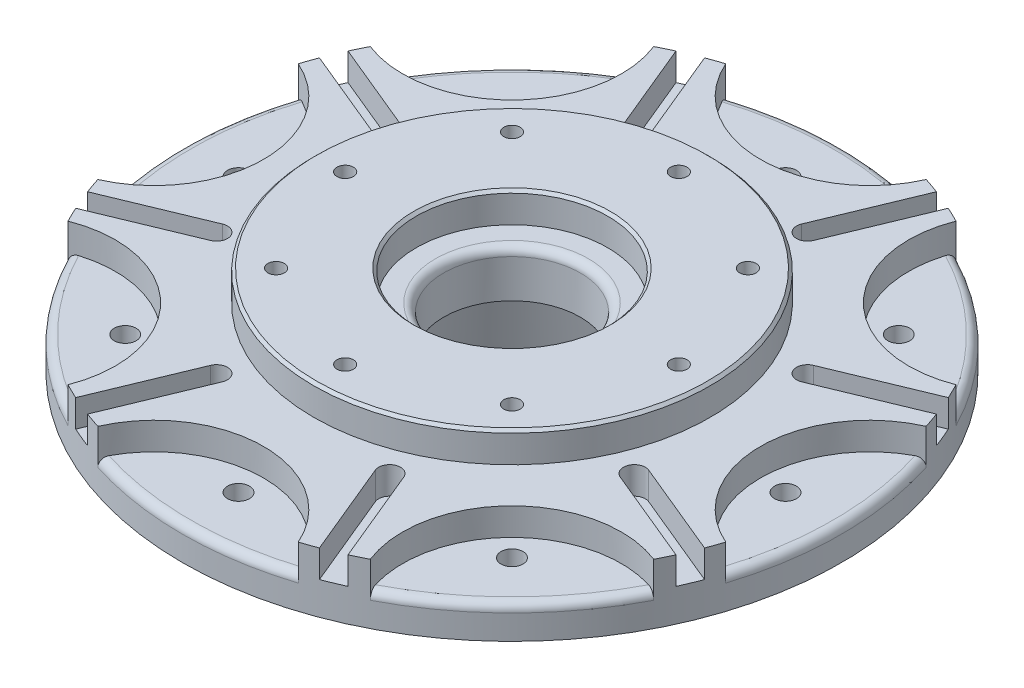
SolidWorks part; units mm, degrees
material "Plain Carbon Steel"
ref_plane "Front Plane" through (0, 0, 0) normal (0, 0, 1) x (1, 0, 0)
ref_plane "Top Plane" through (0, 0, 0) normal (0, 1, 0) x (1, 0, 0)
ref_plane "Right Plane" through (0, 0, 0) normal (1, 0, 0) x (0, 0, -1)
sketch "Sketch2" plane through (0, 0, 0) normal (0, 1, 0) x (1, 0, 0)
  circle A0 centre (0, 0) radius 72.5
  circle A1 centre (0, 0) radius 120.5
  dimension "D1" = 145
  dimension "D2" = 241
extrude "Boss-Extrude5" add sketch "Sketch2" along normal blind 11 contours A0 region at (0, 0, 0)
extrude "Boss-Extrude6" add sketch "Sketch2<8>" against normal blind 22 separate body contours A1 A0 region at (-117.0917, 0, 0)
sketch "Sketch2<8>" plane through (0, 0, 0) normal (0, 1, 0) x (1, 0, 0) same geometry as "Sketch2"
sketch "Sketch4" plane through (0, 0, 0) normal (0, -1, 0) x (1, 0, 0)
  circle A0 centre (0, 0) radius 74
extrude "Boss-Extrude7" add sketch "Sketch4" along normal blind 54
sketch "Sketch5" plane through (0, 11, 0) normal (0, 1, 0) x (1, 0, 0)
  circle A0 centre (0, 0) radius 35
  dimension "D1" = 70
extrude "Cut-Extrude2" cut sketch "Sketch5" against normal blind 11
sketch "Sketch6" plane through (0, 0, 0) normal (0, 1, 0) x (1, 0, 0)
  circle A0 centre (0, 0) radius 25
  dimension "D1" = 50
chamfer "Chamfer1" distance 1 angle 45 1 edges at (0, 11, 35)
extrude "Cut-Extrude3" cut sketch "Sketch6" against normal blind 65 contours A0
fillet "Fillet1" radius 3 1 edges at (0, 0, 25)
sketch "Sketch7" plane through (0, 0, 0) normal (0, 1, 0) x (1, 0, 0)
  line L0 (0, 0) -> (0, 130.84) construction
  circle A0 centre (0, 130.84) radius 40
  circle A1 centre (92.5179, 92.5179) radius 40
  circle A2 centre (130.84, 0) radius 40
  circle A3 centre (92.5179, -92.5179) radius 40
  circle A4 centre (0, -130.84) radius 40
  circle A5 centre (-92.5179, -92.5179) radius 40
  circle A6 centre (-130.84, 0) radius 40
  circle A7 centre (-92.5179, 92.5179) radius 40
  point P21 (0, 0)
  dimension "D1" = 80
  dimension "D2" = 130.84
  dimension "D3" = 8
extrude "Cut-Extrude4" cut sketch "Sketch7" against normal blind 10
fillet "Fillet2" radius 3 8 edges at (0, -10, -120.5) (85.2064, -10, -85.2064) (120.5, -10, 0) (85.2064, -10, 85.2064) (0, -10, 120.5) (-85.2064, -10, 85.2064) (-120.5, -10, 0) (-85.2064, -10, -85.2064)
chamfer "Chamfer2" distance 1 angle 45 1 edges at (0, 11, 72.5)
sketch "Sketch8" plane through (0, -54, 0) normal (0, -1, 0) x (1, 0, 0)
  circle A0 centre (0, 0) radius 43
  dimension "D1" = 86
extrude "Cut-Extrude5" cut sketch "Sketch8" against normal blind 44
sketch "Sketch9" plane through (0, -54, 0) normal (0, -1, 0) x (1, 0, 0)
  circle A0 centre (0, 0) radius 49.17
  dimension "D1" = 98.34
extrude "Cut-Extrude8" cut sketch "Sketch9" against normal blind 35 draft 10
sketch "Sketch12" plane through (0, -10, 0) normal (0, -1, 0) x (1, 0, 0)
  circle A0 centre (0, 0) radius 35
  circle A2 centre (0, 0) radius 25 construction
  circle A3 centre (0, 0) radius 25
  dimension "D2" = 70
extrude "Boss-Extrude9" add sketch "Sketch12" along normal blind 7
sketch "Sketch13" plane through (0, 0, 0) normal (0, 1, 0) x (1, 0, 0)
  line L0 (0, 0) -> (0, -157.3965) construction
  line L1 (0, 0) -> (-63.2958, -152.8097) construction
  line L2 (-35.3434, -74.8741) -> (-49.8854, -109.9815)
  line L3 (-27.9524, -77.9356) -> (-42.4944, -113.043)
  line L4 (-77.9356, -27.9524) -> (-113.043, -42.4944)
  line L5 (-74.8741, -35.3434) -> (-109.9815, -49.8854)
  line L6 (-74.8741, 35.3434) -> (-109.9815, 49.8854)
  line L7 (-77.9356, 27.9524) -> (-113.043, 42.4944)
  line L8 (-27.9524, 77.9356) -> (-42.4944, 113.043)
  line L9 (-35.3434, 74.8741) -> (-49.8854, 109.9815)
  line L10 (35.3434, 74.8741) -> (49.8854, 109.9815)
  line L11 (27.9524, 77.9356) -> (42.4944, 113.043)
  line L12 (77.9356, 27.9524) -> (113.043, 42.4944)
  line L13 (74.8741, 35.3434) -> (109.9815, 49.8854)
  line L14 (74.8741, -35.3434) -> (109.9815, -49.8854)
  line L15 (77.9356, -27.9524) -> (113.043, -42.4944)
  line L16 (27.9524, -77.9356) -> (42.4944, -113.043)
  line L17 (35.3434, -74.8741) -> (49.8854, -109.9815)
  arc A1 (-27.9524, -77.9356) -> (-35.3434, -74.8741) centre (-31.6479, -76.4048) ccw
  arc A3 (-49.8854, -109.9815) -> (-42.4944, -113.043) centre (-46.1899, -111.5123) ccw
  arc A4 (-74.8741, -35.3434) -> (-77.9356, -27.9524) centre (-76.4048, -31.6479) ccw
  arc A5 (-113.043, -42.4944) -> (-109.9815, -49.8854) centre (-111.5123, -46.1899) ccw
  arc A6 (-77.9356, 27.9524) -> (-74.8741, 35.3434) centre (-76.4048, 31.6479) ccw
  arc A7 (-109.9815, 49.8854) -> (-113.043, 42.4944) centre (-111.5123, 46.1899) ccw
  arc A8 (-35.3434, 74.8741) -> (-27.9524, 77.9356) centre (-31.6479, 76.4048) ccw
  arc A9 (-42.4944, 113.043) -> (-49.8854, 109.9815) centre (-46.1899, 111.5123) ccw
  arc A10 (27.9524, 77.9356) -> (35.3434, 74.8741) centre (31.6479, 76.4048) ccw
  arc A11 (49.8854, 109.9815) -> (42.4944, 113.043) centre (46.1899, 111.5123) ccw
  arc A12 (74.8741, 35.3434) -> (77.9356, 27.9524) centre (76.4048, 31.6479) ccw
  arc A13 (113.043, 42.4944) -> (109.9815, 49.8854) centre (111.5123, 46.1899) ccw
  arc A14 (77.9356, -27.9524) -> (74.8741, -35.3434) centre (76.4048, -31.6479) ccw
  arc A15 (109.9815, -49.8854) -> (113.043, -42.4944) centre (111.5123, -46.1899) ccw
  arc A16 (35.3434, -74.8741) -> (27.9524, -77.9356) centre (31.6479, -76.4048) ccw
  arc A17 (42.4944, -113.043) -> (49.8854, -109.9815) centre (46.1899, -111.5123) ccw
  point P54 (0, 0)
  dimension "D2" = 8
  dimension "D4" = 38
  dimension "D3" = 8
  dimension "D1" = 22.5
  dimension "D5" = 8
extrude "Cut-Extrude9" cut sketch "Sketch13" against normal blind 10
sketch "Sketch14" plane through (0, 11, 0) normal (0, 1, 0) x (1, 0, 0)
  line L0 (0, 0) -> (-184.5514, 0) construction
  circle A0 centre (-61, 0) radius 3
  circle A1 centre (-43.1335, 43.1335) radius 3
  circle A2 centre (0, 61) radius 3
  circle A3 centre (43.1335, 43.1335) radius 3
  circle A4 centre (61, 0) radius 3
  circle A5 centre (43.1335, -43.1335) radius 3
  circle A6 centre (0, -61) radius 3
  circle A7 centre (-43.1335, -43.1335) radius 3
  point P22 (0, 0)
  dimension "D1" = 6
  dimension "D2" = 61
  dimension "D3" = 8
extrude "Cut-Extrude10" cut sketch "Sketch14" against normal blind 21
sketch "Sketch15" plane through (0, -54, 0) normal (0, -1, 0) x (1, 0, 0)
  line L0 (0, 0) -> (-149.7637, 0) construction
  circle A0 centre (-61, 0) radius 6
  circle A1 centre (-43.1335, 43.1335) radius 6
  circle A2 centre (0, 61) radius 6
  circle A3 centre (43.1335, 43.1335) radius 6
  circle A4 centre (61, 0) radius 6
  circle A5 centre (43.1335, -43.1335) radius 6
  circle A6 centre (0, -61) radius 6
  circle A7 centre (-43.1335, -43.1335) radius 6
  point P21 (0, 0)
  dimension "D1" = 12
  dimension "D2" = 61
  dimension "D3" = 8
extrude "Cut-Extrude11" cut sketch "Sketch15" against normal blind 44
sketch "Sketch16" plane through (0, -10, 0) normal (0, 1, 0) x (1, 0, 0)
  line L0 (0, 0) -> (0, -147.5763) construction
  circle A0 centre (0, -100) radius 4
  circle A1 centre (-70.7107, -70.7107) radius 4
  circle A2 centre (-100, 0) radius 4
  circle A3 centre (-70.7107, 70.7107) radius 4
  circle A4 centre (0, 100) radius 4
  circle A5 centre (70.7107, 70.7107) radius 4
  circle A6 centre (100, 0) radius 4
  circle A7 centre (70.7107, -70.7107) radius 4
  point P21 (0, 0)
  dimension "D1" = 100
  dimension "D2" = 8
  dimension "D3" = 8
extrude "Cut-Extrude14" cut sketch "Sketch16" against normal blind 44
